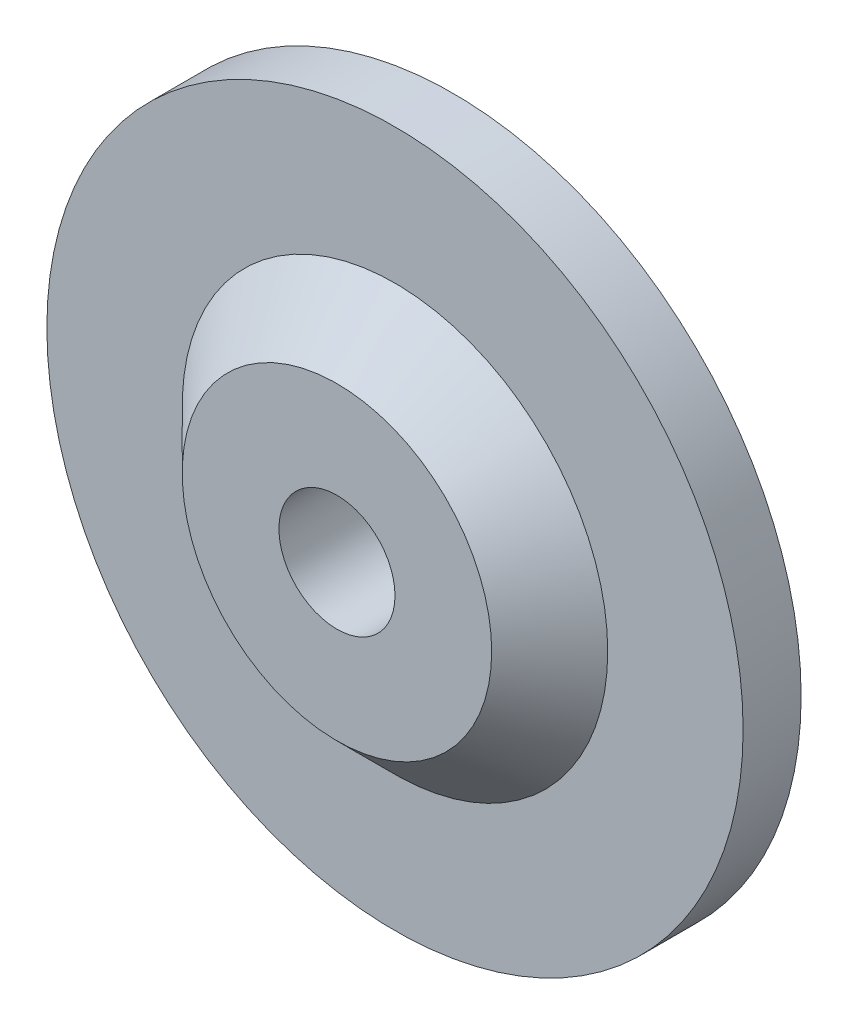
SolidWorks part; units mm, degrees
ref_plane "Plan de face" through (0, 0, 0) normal (0, 0, 1) x (1, 0, 0)
ref_plane "Plan de dessus" through (0, 0, 0) normal (0, 1, 0) x (1, 0, 0)
ref_plane "Plan de droite" through (0, 0, 0) normal (1, 0, 0) x (0, 0, -1)
sketch "Esquisse1" plane through (0, 0, 0) normal (0, 0, 1) x (1, 0, 0)
  circle A0 centre (0, 0) radius 18
  circle A1 centre (0, 0) radius 3
  dimension "D1" = 6
  dimension "D2" = 36
extrude "Boss.-Extru.1" add sketch "Esquisse1" along normal blind 3
sketch "Esquisse2" plane through (0, 0, 3) normal (0, 0, 1) x (1, 0, 0)
  circle A0 centre (0, 0) radius 3 construction
  circle A1 centre (0, 0) radius 3
  circle A2 centre (0, 0) radius 13
  dimension "D1" = 10
extrude "Boss.-Extru.2" add sketch "Esquisse2" along normal blind 3
chamfer "Chanfrein1" distance 5 angle 45 1 edges at (13, 0, 6)
